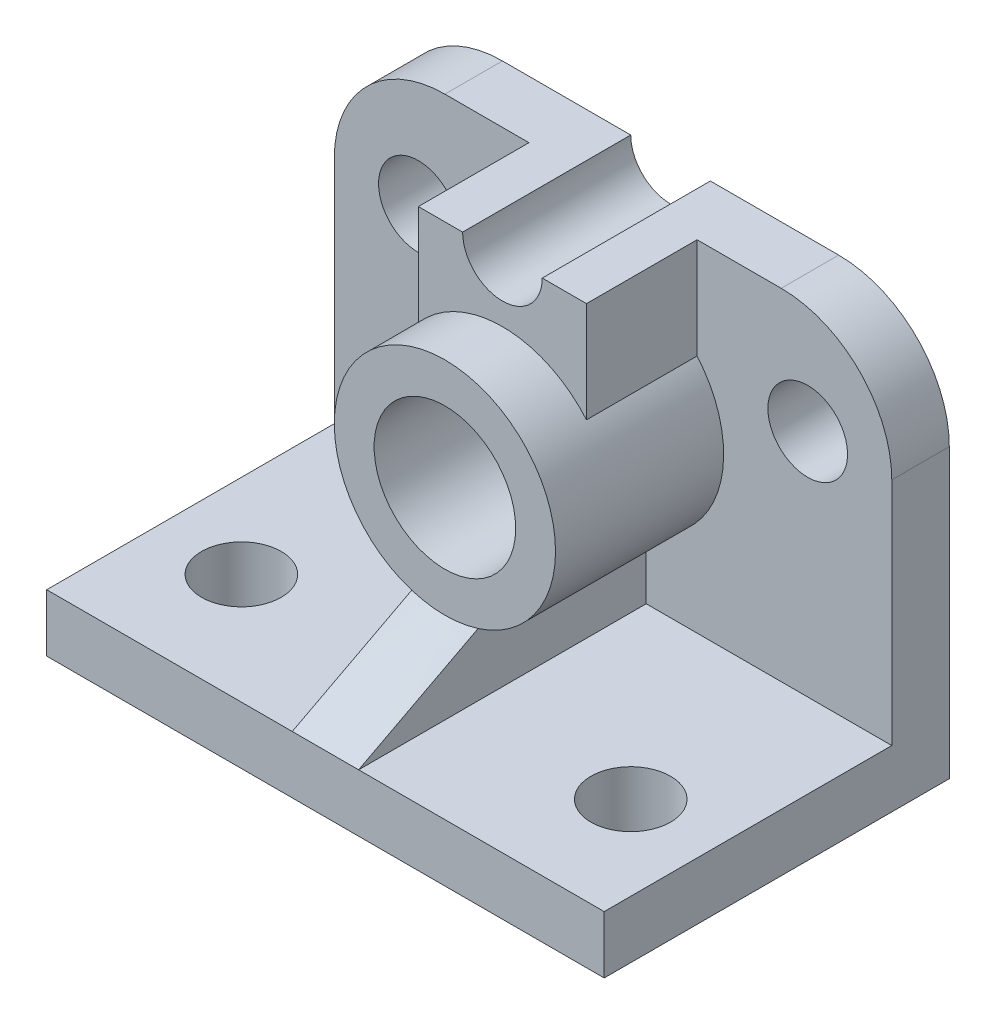
SolidWorks part; units mm, degrees
ref_plane "Front Plane" through (0, 0, 0) normal (0, 0, 1) x (1, 0, 0)
ref_plane "Top Plane" through (0, 0, 0) normal (0, 1, 0) x (1, 0, 0)
ref_plane "Right Plane" through (0, 0, 0) normal (1, 0, 0) x (0, 0, -1)
sketch "Sketch1" plane through (0, 0, 0) normal (0, 0, 1) x (1, 0, 0)
  line L0 (0, -6.5) -> (0, 83.5) construction
  line L1 (-63, 6.5) -> (63, 6.5)
  line L2 (-63, 6.5) -> (-63, -6.5)
  line L3 (-63, -6.5) -> (63, -6.5)
  line L4 (63, 6.5) -> (63, -6.5)
  line L5 (-63, 6.5) -> (63, -6.5) construction
  line L6 (-63, -6.5) -> (63, 6.5) construction
  line L7 (-63, 6.5) -> (63, 6.5)
  line L8 (-63, 6.5) -> (-63, 83.5)
  line L9 (-63, 83.5) -> (-9, 83.5)
  line L10 (63, 6.5) -> (63, 83.5)
  line L11 (-9, 83.5) -> (-19, 83.5)
  line L12 (-19, 83.5) -> (-19, 60.7481)
  line L13 (9, 83.5) -> (19, 83.5)
  line L14 (19, 83.5) -> (19, 60.7481)
  line L15 (9, 83.5) -> (63, 83.5)
  circle A0 centre (-44, 58.5) radius 9
  circle A1 centre (44, 58.5) radius 9
  circle A2 centre (0, 44.5) radius 25
  circle A3 centre (0, 44.5) radius 16
  arc A4 (-9, 83.5) -> (9, 83.5) centre (0, 83.5) ccw
  point P0 (0, 0)
  point P17 (0, 6.5)
  dimension "D6" = 18
  dimension "D8" = 32
  dimension "D9" = 50
  dimension "D10" = 9
  dimension "D1" = 126
  dimension "D2" = 13
  dimension "D3" = 90
  dimension "D4" = 25
  dimension "D5" = 19
  dimension "D7" = 38
  dimension "D11" = 10
extrude "Boss-Extrude1" add sketch "Sketch1" along normal blind 78 contours L4 L1 L2 L3 region at (0, 0, 0)
extrude "Boss-Extrude2" add sketch "Sketch1<3>" along normal blind 13 contours A2 L12 L9 L8 L1 L10 L15 L14 A0 A1 region at (-61.5233, 45, 0)
sketch "Sketch1<3>" plane through (0, 0, 0) normal (0, 0, 1) x (1, 0, 0) same geometry as "Sketch1"
extrude "Boss-Extrude3" add sketch "Sketch1<4>" along normal blind 51 contours A2 A3 region at (0, 68.7929, 0)
sketch "Sketch1<4>" plane through (0, 0, 0) normal (0, 0, 1) x (1, 0, 0) same geometry as "Sketch1"
extrude "Boss-Extrude4" add sketch "Sketch1<5>" along normal blind 38 contours A4 L9 L12 A2 L14 L13 region at (0, 73.7887, 0)
sketch "Sketch1<5>" plane through (0, 0, 0) normal (0, 0, 1) x (1, 0, 0) same geometry as "Sketch1"
sketch "Sketch2" plane through (0, 6.5, 0) normal (0, 1, 0) x (1, 0, 0)
  line L0 (-63, -78) -> (63, -78) construction
  line L1 (-63, -78) -> (-63, -13) construction
  line L2 (0, 0) -> (0, -78) construction
  circle A0 centre (-44, -53) radius 9
  circle A1 centre (44, -53) radius 9
  dimension "D3" = 18
  dimension "D1" = 25
  dimension "D2" = 19
extrude "Cut-Extrude1" cut sketch "Sketch2" against normal through all
fillet "Fillet1" radius 25 2 edges at (-63, 83.5, 6.5) (63, 83.5, 6.5)
ref_plane "Plane1" through (7.5, 0, 0) normal (1, 0, 0) x (0, 0, -1)
ref_plane "Plane2" through (-7.5, 0, 0) normal (1, 0, 0) x (0, 0, -1)
sketch "Sketch4" plane through (-7.5, 0, 0) normal (1, 0, 0) x (0, 0, -1)
  line L0 (-78, 6.5) -> (-51, 20.6515)
  line L3 (-51, 20.6515) -> (-13, 20.6515)
  line L4 (-13, 6.5) -> (-13, 58.5) construction
  line L5 (-13, 20.6515) -> (-13, 6.5)
  line L6 (-13, 6.5) -> (-78, 6.5)
sketch "Sketch5" plane through (7.5, 0, 0) normal (1, 0, 0) x (0, 0, -1)
  line L0 (-78, 6.5) -> (-51, 20.6515)
  line L3 (-51, 20.6515) -> (-13, 20.6515)
  line L4 (-13, 60.7481) -> (-13, 19.5) construction
  line L5 (-13, 20.6515) -> (-13, 6.5)
  line L6 (-13, 6.5) -> (-78, 6.5)
sketch "Sketch6" plane through (0, 0, 0) normal (1, 0, 0) x (0, 0, -1)
  line L0 (-78, 6.5) -> (-51, 19.5)
  line L1 (-51, 19.5) -> (-13, 19.5)
  line L2 (-13, 6.5) -> (-13, 58.5) construction
  line L3 (-13, 19.5) -> (-13, 6.5)
  line L4 (-78, 6.5) -> (-13, 6.5) construction
  line L5 (-13, 6.5) -> (-78, 6.5)
loft "Loft4" add profiles "Sketch4", "Sketch6", "Sketch5" start constraint default end constraint default connector at (-7.5, 6.5, 78) connector at (0, 6.5, 78) connector at (7.5, 6.5, 78)
